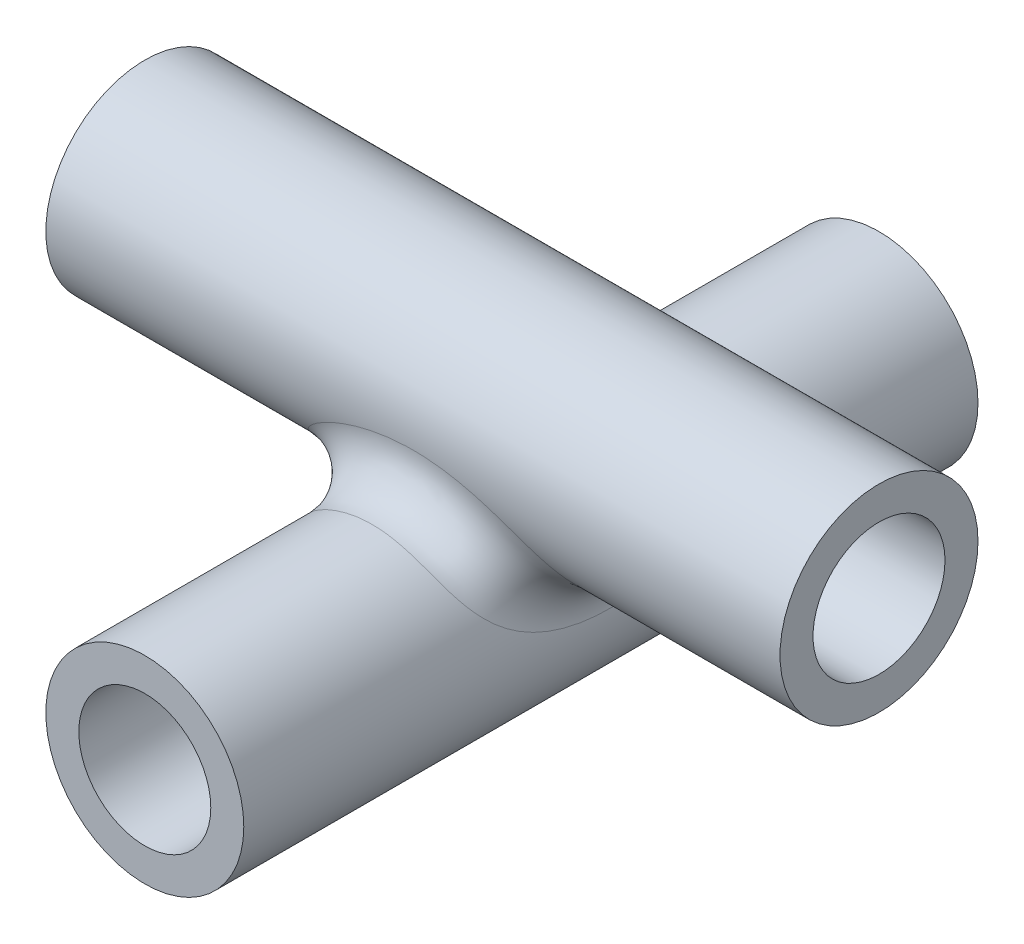
SolidWorks part; units mm, degrees
ref_plane "Front Plane" through (0, 0, 0) normal (0, 0, 1) x (1, 0, 0)
ref_plane "Top Plane" through (0, 0, 0) normal (0, 1, 0) x (1, 0, 0)
ref_plane "Right Plane" through (0, 0, 0) normal (1, 0, 0) x (0, 0, -1)
sketch "Sketch2" plane through (0, 0, 0) normal (0, 0, 1) x (1, 0, 0)
  circle A0 centre (0, 0) radius 12
  circle A1 centre (0, 0) radius 8
  dimension "D1" = 24
  dimension "D2" = 16
extrude "Boss-Extrude1" add sketch "Sketch2" along normal blind 89
sketch "Sketch4" plane through (0, 0, 0) normal (1, 0, 0) x (0, 0, -1)
  line L0 (0, 0) -> (-110.4148, 0) construction
  line L1 (-44.5, 12) -> (-44.5, -24.4866) construction
  line L2 (0, 12) -> (-89, 12) construction
  line L3 (-89, -12) -> (0, -12) construction
  circle A0 centre (-44.5, 18) radius 8
  circle A1 centre (-44.5, 18) radius 12
  dimension "D1" = 16
  dimension "D2" = 24
  dimension "30" = 30
extrude "Boss-Extrude2" add sketch "Sketch4" along normal mid plane 89
fillet "Fillet1" radius 5 1 edges at (-2.2672, 11.7839, 34.2355)
